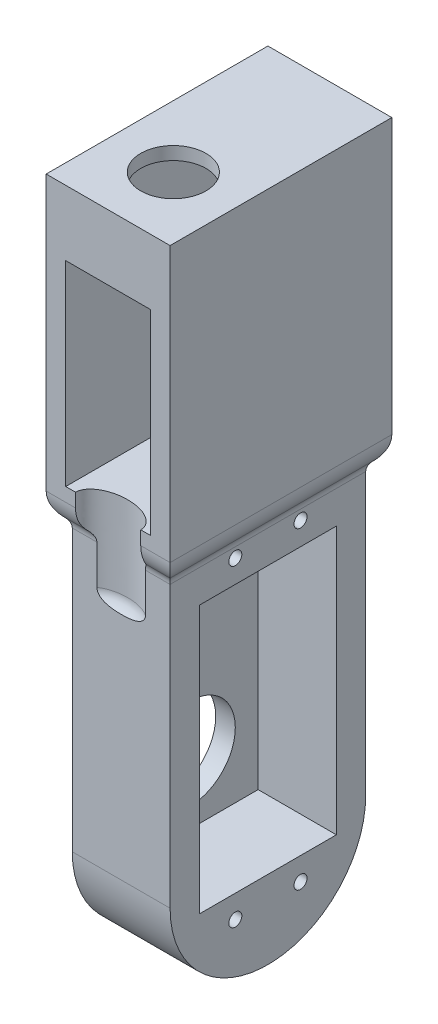
SolidWorks part; units mm, degrees
ref_plane "Front Plane" through (0, 0, 0) normal (0, 0, 1) x (1, 0, 0)
ref_plane "Top Plane" through (0, 0, 0) normal (0, 1, 0) x (1, 0, 0)
ref_plane "Right Plane" through (0, 0, 0) normal (1, 0, 0) x (0, 0, -1)
sketch "Sketch1" plane through (0, 0, 0) normal (1, 0, 0) x (0, 0, -1)
  line L8 (15, 0) -> (15, 45)
  line L9 (-15, 0) -> (-15, 45)
  line L14 (-15, 45) -> (15, 45)
  arc A0 (-15, 0) -> (15, 0) centre (0, 0) ccw
extrude "Boss-Extrude1" add sketch "Sketch1" along normal blind 15
sketch "Sketch2" plane through (15, 0, 0) normal (1, 0, 0) x (0, 0, -1)
  line L0 (-10.5, -3) -> (-10.5, 38)
  line L7 (-10.5, 38) -> (10.5, 38)
  line L8 (10.5, 38) -> (10.5, -3)
  line L9 (10.5, -3) -> (-10.5, -3)
extrude "Cut-Extrude1" cut sketch "Sketch2" against normal blind 12
sketch "Sketch3" plane through (3, 0, 0) normal (1, 0, 0) x (0, 0, -1)
  circle A0 centre (0, 7) radius 7
extrude "Cut-Extrude2" cut sketch "Sketch3" against normal blind 6
sketch "Sketch4" plane through (15, 0, 0) normal (1, 0, 0) x (0, 0, -1)
  circle A0 centre (-5, 41.5) radius 1
  circle A1 centre (5, 41.5) radius 1
  circle A2 centre (-5, -6.5) radius 1
  circle A3 centre (5, -6.5) radius 1
extrude "Cut-Extrude3" cut sketch "Sketch4" against normal blind 5
sketch "Sketch6" plane through (0, 45, 0) normal (0, 1, 0) x (1, 0, 0)
  line L1 (17, -17) -> (17, 17)
  line L8 (-2, -17) -> (-2, 17)
  line L9 (17, 17) -> (-2, 17)
  line L11 (-2, -17) -> (17, -17)
extrude "Boss-Extrude2" add sketch "Sketch6" along normal blind 45
sketch "Sketch11" plane through (0, 0, 17) normal (0, 0, 1) x (1, 0, 0)
  line L0 (14, 80) -> (1, 80)
  line L1 (14, 80) -> (14, 50)
  line L5 (1, 50) -> (1, 80)
  line L6 (14, 50) -> (1, 50)
extrude "Cut-Extrude9" cut sketch "Sketch11" against normal blind 37
sketch "Sketch13" plane through (0, 80, 0) normal (0, -1, 0) x (1, 0, 0)
  line L0 (14, -12) -> (1, -12)
  line L3 (14, -12) -> (14, 12)
  line L4 (14, 12) -> (1, 12)
  line L5 (1, 12) -> (1, -12)
extrude "Cut-Extrude10" cut sketch "Sketch13" against normal blind 8
sketch "Sketch14" plane through (0, 80, 0) normal (0, -1, 0) x (1, 0, 0)
  circle A2 centre (7.5, -14.5) radius 1
extrude "Cut-Extrude11" cut sketch "Sketch14" against normal blind 5
sketch "Sketch15" plane through (0, 80, 0) normal (0, -1, 0) x (1, 0, 0)
  circle A0 centre (7.5, 14.5) radius 1
extrude "Cut-Extrude12" cut sketch "Sketch15" against normal blind 5
fillet "Fillet1" radius 2 2 edges at (0, 45, 0) (15, 45, 0)
fillet "Fillet2" radius 2 2 edges at (7.5, 45, 15) (7.5, 45, -15)
fillet "Fillet3" radius 5 4 edges at (7.5, 45, 17) (-2, 45, 0) (7.5, 45, -17) (17, 45, 0)
sketch "Sketch16" plane through (0, 50, 0) normal (0, 1, 0) x (1, 0, 0)
  line L0 (1, 17) -> (14, 17) construction
  line L2 (1, -17) -> (14, -17) construction
  ellipse E0 centre (7.5, 17) end of major axis (12.5, 17) minor radius 3
  ellipse E1 centre (7.5, -17) end of major axis (12.5, -17) minor radius 3
extrude "Cut-Extrude13" cut sketch "Sketch16" against normal blind 15
fillet "Fillet7" radius 2 2 edges at (7.5, 35, 14) (7.5, 35, -14)
sketch "Sketch17" plane through (0, 90, 0) normal (0, 1, 0) x (1, 0, 0)
  circle A0 centre (7.5, -7) radius 5
extrude "Cut-Extrude14" cut sketch "Sketch17" against normal blind 2
